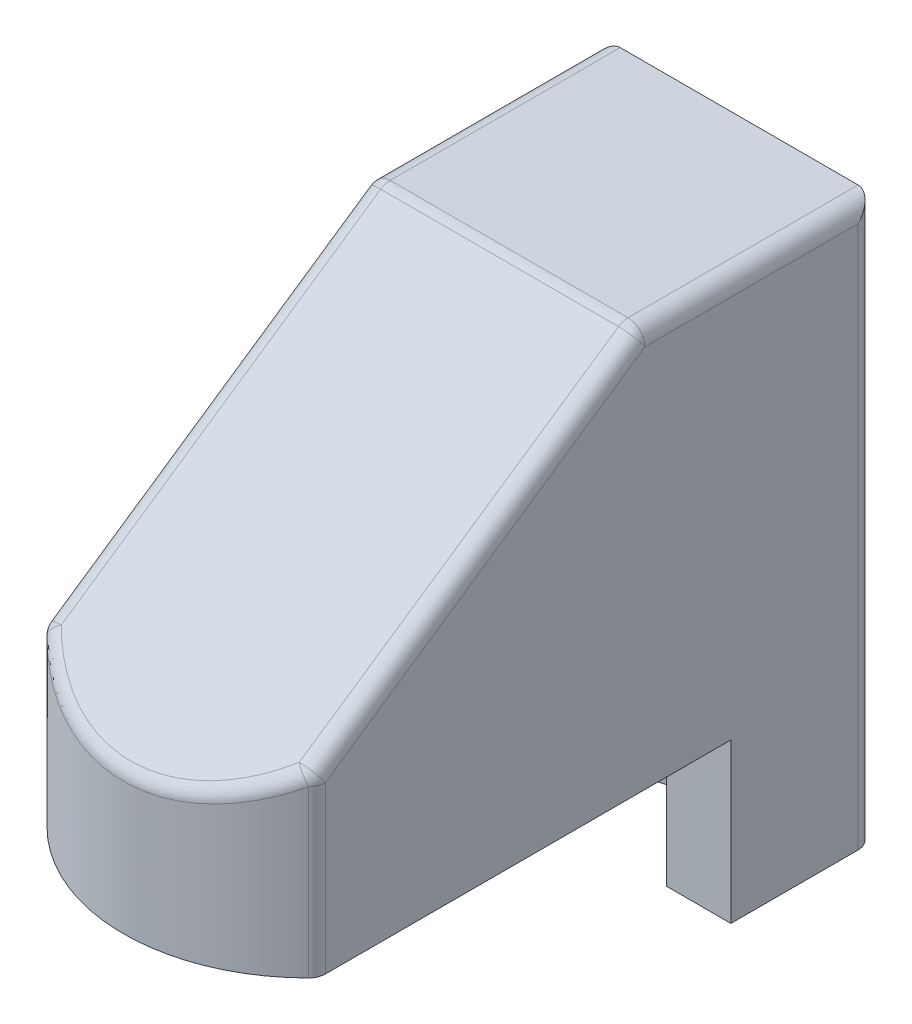
SolidWorks part; units mm, degrees
ref_plane "Front Plane" through (0, 0, 0) normal (0, 0, 1) x (1, 0, 0)
ref_plane "Top Plane" through (0, 0, 0) normal (0, 1, 0) x (1, 0, 0)
ref_plane "Right Plane" through (0, 0, 0) normal (1, 0, 0) x (0, 0, -1)
sketch "Sketch1" plane through (0, 0, 0) normal (0, 1, 0) x (1, 0, 0)
  line L0 (0, 0) -> (8.08, 0)
  line L1 (8.08, 0) -> (8.08, -16.55)
  line L2 (0, 0) -> (0, -16.55)
  line L3 (4.04, -18.32) -> (-7.2213, -18.32) construction
  arc A0 (0, -16.55) -> (8.08, -16.55) centre (4.04, -12.8244) ccw
  dimension "D3" = 18.32
  dimension "D1" = 8.08
  dimension "D2" = 16.55
extrude "Boss-Extrude1" add sketch "Sketch1" along normal blind 11.91
sketch "Sketch2" plane through (8.08, 0, 0) normal (1, 0, 0) x (0, 0, -1)
  line L0 (-7, 11.91) -> (-16.55, 5.4)
  line L1 (-16.55, 11.91) -> (0, 11.91) construction
  line L2 (-16.55, 11.91) -> (-16.55, 0) construction
  line L3 (0, 11.91) -> (0, 0) construction
  line L4 (-16.55, 0) -> (0, 0) construction
  line L5 (-16.55, 5.4) -> (-22.0573, 1.6458)
  line L6 (-22.0573, 1.6458) -> (-22.0573, 16.5751)
  line L7 (-22.0573, 16.5751) -> (-7, 16.5751)
  line L8 (-7, 16.5751) -> (-7, 11.91)
  dimension "D1" = 7
  dimension "D2" = 5.4
extrude "Cut-Extrude1" cut sketch "Sketch2" against normal up to surface (8.08 mm away) up to face at (0, 5.955, 8.275)
sketch "Sketch3" plane through (0, 0, 0) normal (0, -1, 0) x (1, 0, 0)
  line L0 (0, 0) -> (0, 16.55) construction
  line L1 (8.08, 0) -> (0, 0)
  line L2 (8.08, 0) -> (8.08, 7.57)
  line L3 (8.08, 7.57) -> (0, 7.57)
  line L4 (0, 0) -> (0, 7.57)
  dimension "D1" = 7.57
extrude "Boss-Extrude2" add sketch "Sketch3" along normal blind 4.73
sketch "Sketch4" plane through (0, 0, 0) normal (0, -1, 0) x (1, 0, 0)
  line L1 (8.08, 16.55) -> (8.08, 7.57) construction
  line L2 (8.08, 7.57) -> (0, 7.57) construction
  circle A0 centre (4.04, 11.32) radius 2.945
  dimension "D1" = 5.89
  dimension "D2" = 4.04
  dimension "D3" = 3.75
extrude "Boss-Extrude3" add sketch "Sketch4" along normal blind 0.64
sketch "Sketch5" plane through (0, -4.73, 0) normal (0, -1, 0) x (1, 0, 0)
  line L0 (8.08, 0) -> (8.08, 7.57) construction
  line L1 (0, 0) -> (8.08, 0) construction
  circle A0 centre (4.04, 3.785) radius 2.175
  dimension "D1" = 4.35
  dimension "D2" = 4.04
  dimension "D3" = 3.785
extrude "Cut-Extrude2" cut sketch "Sketch5" against normal blind 13.11
fillet "Fillet1" radius 0.5 12 edges at (0, -2.365, 7.57) (8.08, -2.365, 7.57) (8.08, 3.59, 0) (0, 3.59, 0) (0, 11.91, 3.5) (4.04, 11.91, 7) (8.08, 11.91, 3.5) (8.08, 2.7, 16.55) (0, 2.7, 16.55) (4.04, 4.1934, 18.32) (8.08, 8.655, 11.775) (0, 8.655, 11.775)
sketch "Sketch7" plane through (0, -4.73, 0) normal (0, -1, 0) x (1, 0, 0)
  line L0 (7.58, 7.57) -> (0.5, 7.57) construction
  line L1 (8.08, 7.57) -> (0, 7.57)
  line L2 (8.08, 7.57) -> (8.08, 4.285)
  line L3 (8.08, 4.285) -> (0, 4.285)
  line L4 (0, 7.57) -> (0, 4.285)
  line L5 (8.08, 0.5) -> (8.08, 7.07) construction
  line L6 (0, 7.07) -> (0, 0.5) construction
  line L7 (7.58, 7.57) -> (0.5, 7.57) construction
  dimension "D2" = 3.285
extrude "Cut-Extrude3" cut sketch "Sketch7" against normal up to surface (4.73 mm away) up to face at (4.04, 0, 14.265)
